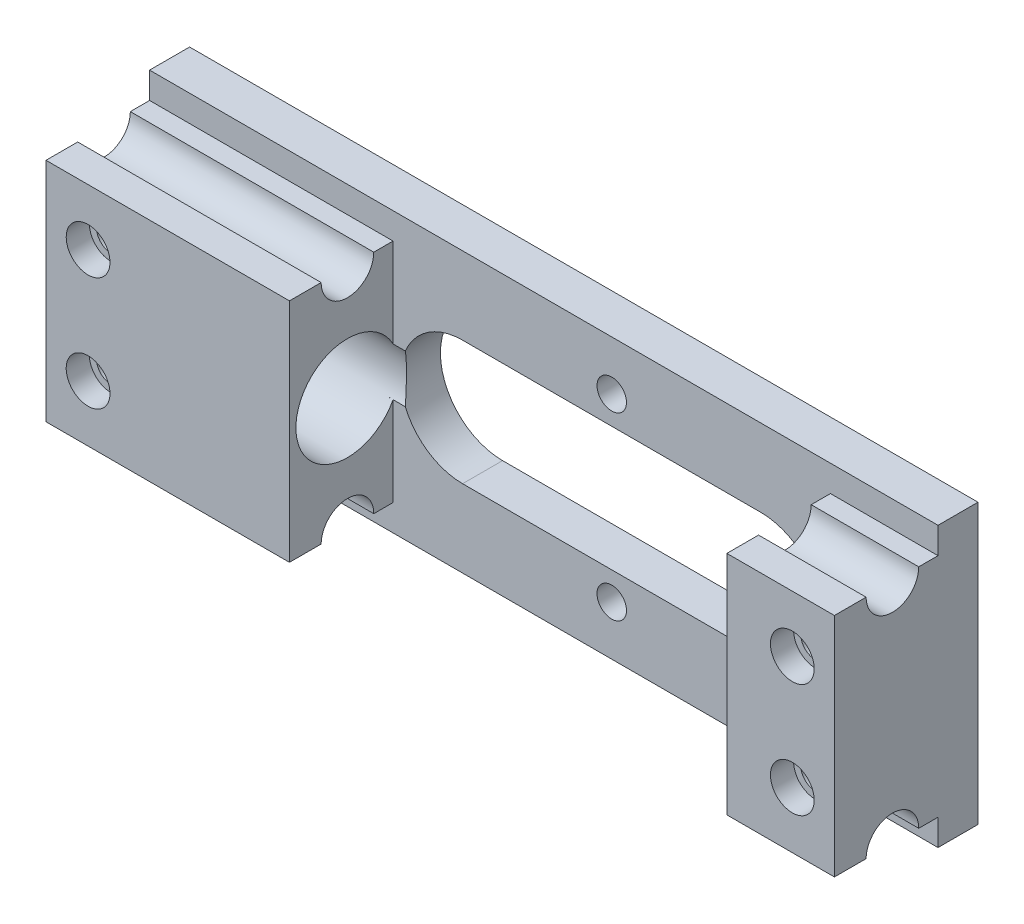
SolidWorks part; units mm, degrees
ref_plane "Front Plane" through (0, 0, 0) normal (0, 0, 1) x (1, 0, 0)
ref_plane "Top Plane" through (0, 0, 0) normal (0, 1, 0) x (1, 0, 0)
ref_plane "Right Plane" through (0, 0, 0) normal (1, 0, 0) x (0, 0, -1)
sketch "Sketch1" plane through (0, 0, 0) normal (0, 0, 1) x (1, 0, 0)
  line L1 (-22.0345, -8.4201) -> (22.0345, -8.4201)
  line L2 (-22.0345, -8.4201) -> (-22.0345, 8.4201)
  line L3 (-22.0345, 8.4201) -> (22.0345, 8.4201)
  line L4 (22.0345, -8.4201) -> (22.0345, 8.4201)
  line L5 (-22.0345, -8.4201) -> (22.0345, 8.4201) construction
  line L6 (-22.0345, 8.4201) -> (22.0345, -8.4201) construction
  point P0 (0, 0)
  dimension "D1" = 44.069
  dimension "D2" = 16.8402
extrude "Boss-Extrude1" add sketch "Sketch1" along normal blind 7.1628
sketch "Sketch2" plane through (0, 0, 7.1628) normal (0, 0, 1) x (1, 0, 0)
  line L0 (-22.0345, 0) -> (22.0345, 0) construction
  line L1 (-10.8458, 8.4201) -> (15.5448, 8.4201)
  line L2 (-10.8458, 8.4201) -> (-10.8458, -8.4201)
  line L3 (-10.8458, -8.4201) -> (15.5448, -8.4201)
  line L4 (15.5448, 8.4201) -> (15.5448, -8.4201)
  line L5 (-22.0345, 8.4201) -> (-22.0345, -8.4201) construction
  line L6 (22.0345, -8.4201) -> (22.0345, 8.4201) construction
  line L7 (-10.8458, 8.4201) -> (-22.0345, 0) construction
  line L8 (-22.0345, 0) -> (-10.8458, -8.4201) construction
  line L9 (2.3495, 8.4201) -> (2.3495, -8.4201) construction
  line L12 (22.0345, 8.4201) -> (-22.0345, 8.4201) construction
  dimension "D1" = 26.3906
  dimension "D2" = 24.384
extrude "Cut-Extrude1" cut sketch "Sketch2" against normal blind 4.75
sketch "Sketch4" plane through (0, 0, 7.1628) normal (0, 0, 1) x (1, 0, 0)
  line L0 (-10.8458, 8.4201) -> (-10.8458, -8.4201) construction
  line L1 (-22.0345, -8.4201) -> (-10.8458, -8.4201)
  line L2 (-22.0345, -8.4201) -> (-22.0345, -6.8326)
  line L3 (-22.0345, -6.8326) -> (-10.8458, -6.8326)
  line L4 (-10.8458, -8.4201) -> (-10.8458, -6.8326)
  line L5 (-22.0345, 0) -> (-10.8458, 0) construction
  line L6 (-22.0345, 8.4201) -> (-22.0345, -8.4201) construction
  line L7 (-10.8458, 8.4201) -> (-10.8458, -8.4201) construction
  line L8 (-10.8458, 8.4201) -> (-10.8458, 6.8326)
  line L9 (-22.0345, 6.8326) -> (-10.8458, 6.8326)
  line L10 (-22.0345, 8.4201) -> (-22.0345, 6.8326)
  line L11 (-22.0345, 8.4201) -> (-10.8458, 8.4201)
  line L12 (22.0345, -8.4201) -> (22.0345, 8.4201) construction
  line L13 (15.5448, -8.4201) -> (22.0345, -8.4201)
  line L14 (15.5448, -8.4201) -> (15.5448, -6.8326)
  line L15 (15.5448, -6.8326) -> (22.0345, -6.8326)
  line L16 (22.0345, -8.4201) -> (22.0345, -6.8326)
  line L17 (15.5448, 6.8326) -> (22.0345, 6.8326)
  line L18 (22.0345, 8.4201) -> (22.0345, 6.8326)
  line L19 (15.5448, 8.4201) -> (22.0345, 8.4201)
  line L20 (15.5448, 8.4201) -> (15.5448, 6.8326)
  dimension "D1" = 1.5875
extrude "Cut-Extrude9" cut sketch "Sketch4" against normal up to surface (4.75 mm away) up to face at (2.3495, 0, 2.4128)
sketch "Sketch5" plane through (-22.0345, 0, 0) normal (-1, 0, 0) x (0, 0, 1)
  line L1 (0, 0) -> (7.1628, 0) construction
  line L2 (0, 8.4201) -> (0, -8.4201) construction
  line L3 (7.1628, 6.8326) -> (7.1628, -6.8326) construction
  circle A0 centre (5.1628, -6.8326) radius 1.5875
  circle A1 centre (5.1628, 6.8326) radius 1.5875
  dimension "D1" = 3.175
  dimension "D2" = 2
extrude "Cut-Extrude10" cut sketch "Sketch5" against normal through all
sketch "Sketch14" plane through (0, 0, 7.1628) normal (0, 0, 1) x (1, 0, 0)
  line L4 (-10.8458, -6.8326) -> (-10.8458, 6.8326)
  line L5 (-10.8458, 6.8326) -> (-22.0345, 6.8326)
  line L6 (-22.0345, 6.8326) -> (-22.0345, -6.8326)
  line L7 (-22.0345, -6.8326) -> (-10.8458, -6.8326)
  line L8 (-10.8458, -6.8326) -> (-10.8458, 6.8326)
  line L9 (-10.8458, 6.8326) -> (-22.0345, 6.8326)
  line L10 (-22.0345, 6.8326) -> (-22.0345, -6.8326)
  line L11 (-22.0345, -6.8326) -> (-10.8458, -6.8326)
  line L12 (22.0345, -6.8326) -> (22.0345, 6.8326)
  line L13 (22.0345, 6.8326) -> (15.5448, 6.8326)
  line L14 (15.5448, 6.8326) -> (15.5448, -6.8326)
  line L15 (15.5448, -6.8326) -> (22.0345, -6.8326)
  line L16 (22.0345, -6.8326) -> (22.0345, 6.8326)
  line L17 (22.0345, 6.8326) -> (15.5448, 6.8326)
  line L18 (15.5448, 6.8326) -> (15.5448, -6.8326)
  line L19 (15.5448, -6.8326) -> (22.0345, -6.8326)
  dimension "D1" = 0
  dimension "D2" = 0
extrude "Boss-Extrude3" add sketch "Sketch14" along normal blind 1.5
sketch "Sketch6" plane through (0, 0, 8.6628) normal (0, 0, 1) x (1, 0, 0)
  line L0 (-22.0345, 0) -> (-10.8458, 0) construction
  line L2 (-10.8458, 6.8326) -> (-10.8458, -6.8326) construction
  line L3 (-22.0345, 6.8326) -> (-22.0345, -6.8326) construction
  circle A0 centre (-14.7955, 3.429) radius 0.889
  circle A1 centre (-14.7955, -3.429) radius 0.889
  circle A2 centre (19.4945, 3.429) radius 0.889
  circle A3 centre (19.4945, -3.429) radius 0.889
  dimension "D1" = 1.778
  dimension "D2" = 6.858
  dimension "D3" = 7.239
  dimension "D4" = 2
extrude "Cut-Extrude11" cut sketch "Sketch6" against normal through all contours A2 | A3 region at (19.4945, 3.429, 8.6628) region at (19.4945, -3.429, 8.6628)
sketch "Sketch7" plane through (0, 0, 8.6628) normal (0, 0, 1) x (1, 0, 0)
  circle A2 centre (19.4945, 3.429) radius 1.3208
  circle A3 centre (19.4945, -3.429) radius 1.3208
extrude "Cut-Extrude12" cut sketch "Sketch7" against normal blind 1.397
sketch "Sketch9" plane through (0, 0, 0) normal (0, 0, -1) x (-1, 0, 0)
  line L0 (22.0345, 8.4201) -> (22.0345, -8.4201) construction
  line L1 (-22.0345, 0) -> (22.0345, 0) construction
  line L2 (-22.0345, -8.4201) -> (-22.0345, 8.4201) construction
  circle A0 centre (-2.3495, 5.4356) radius 0.889
  circle A1 centre (-2.3495, -5.4356) radius 0.889
  dimension "D1" = 1.778
  dimension "D2" = 24.384
  dimension "D3" = 10.8712
extrude "Cut-Extrude13" cut sketch "Sketch9" against normal through all
sketch "Sketch10" plane through (0, 0, 0) normal (0, 0, -1) x (-1, 0, 0)
  line L0 (-22.0345, 0) -> (22.0345, 0) construction
  line L1 (-22.0345, -8.4201) -> (-22.0345, 8.4201) construction
  line L2 (22.0345, 8.4201) -> (22.0345, -8.4201) construction
  circle A0 centre (-2.3495, 5.4356) radius 1.1906
  circle A1 centre (-2.3495, -5.4356) radius 1.1906
  dimension "D1" = 2.3813
extrude "Cut-Extrude14" cut sketch "Sketch10" against normal blind 1
sketch "Sketch11" plane through (0, 0, 0) normal (0, 0, -1) x (-1, 0, 0)
  line L0 (-22.0345, 0) -> (22.0345, 0) construction
  line L1 (-22.0345, -8.4201) -> (-22.0345, 8.4201) construction
  line L2 (22.0345, 8.4201) -> (22.0345, -8.4201) construction
  line L3 (-2.3495, 5.4356) -> (-2.3495, -5.4356) construction
  line L4 (-11.3495, 0) -> (6.6505, 0) construction
  line L5 (-11.3495, 3.75) -> (6.6505, 3.75)
  line L6 (-11.3495, -3.75) -> (6.6505, -3.75)
  arc A0 (-11.3495, 3.75) -> (-11.3495, -3.75) centre (-11.3495, 0) ccw
  arc A1 (6.6505, -3.75) -> (6.6505, 3.75) centre (6.6505, 0) ccw
  point P12 (-2.3495, 0)
  dimension "D1" = 7.5
  dimension "D2" = 18
extrude "Cut-Extrude15" cut sketch "Sketch11" against normal through all
sketch "Sketch12" plane through (-10.8458, 0, 0) normal (1, 0, 0) x (0, 0, -1)
  circle A0 centre (-5.1628, 0) radius 3.1115
  dimension "D1" = 6.223
extrude "Cut-Extrude16" cut sketch "Sketch12" against normal blind 10.922 and the other way up to next
sketch "Sketch15" plane through (-22.0345, 0, 0) normal (-1, 0, 0) x (0, 0, 1)
  line L10 (8.6628, 6.8326) -> (6.7503, 6.8326)
  line L11 (3.5753, 6.8326) -> (2.4128, 6.8326)
  line L12 (2.4128, 6.8326) -> (2.4128, 8.4201)
  line L13 (2.4128, 8.4201) -> (0, 8.4201)
  line L14 (0, 8.4201) -> (0, -8.4201)
  line L15 (0, -8.4201) -> (2.4128, -8.4201)
  line L16 (2.4128, -8.4201) -> (2.4128, -6.8326)
  line L17 (2.4128, -6.8326) -> (3.5753, -6.8326)
  line L18 (6.7503, -6.8326) -> (8.6628, -6.8326)
  line L19 (8.6628, -6.8326) -> (8.6628, 6.8326)
  line L20 (8.6628, 6.8326) -> (6.7503, 6.8326)
  line L21 (3.5753, 6.8326) -> (2.4128, 6.8326)
  line L22 (2.4128, 6.8326) -> (2.4128, 8.4201)
  line L23 (2.4128, 8.4201) -> (0, 8.4201)
  line L24 (0, 8.4201) -> (0, -8.4201)
  line L25 (0, -8.4201) -> (2.4128, -8.4201)
  line L26 (2.4128, -8.4201) -> (2.4128, -6.8326)
  line L27 (2.4128, -6.8326) -> (3.5753, -6.8326)
  line L28 (6.7503, -6.8326) -> (8.6628, -6.8326)
  line L29 (8.6628, -6.8326) -> (8.6628, 6.8326)
  arc A2 (3.5753, 6.8326) -> (6.7503, 6.8326) centre (5.1628, 6.8326) ccw
  arc A3 (6.7503, -6.8326) -> (3.5753, -6.8326) centre (5.1628, -6.8326) ccw
  arc A4 (3.5753, 6.8326) -> (6.7503, 6.8326) centre (5.1628, 6.8326) ccw
  arc A5 (6.7503, -6.8326) -> (3.5753, -6.8326) centre (5.1628, -6.8326) ccw
  dimension "D1" = 0
extrude "Boss-Extrude4" add sketch "Sketch15" along normal blind 3.5
ref_plane "Plane1" through (-1.75, 0, 0) normal (1, 0, 0) x (0, 0, -1)
mirror "Mirror1" about plane through (-1.75, 0, 0) normal (1, 0, 0) of "Cut-Extrude11", "Cut-Extrude12"
